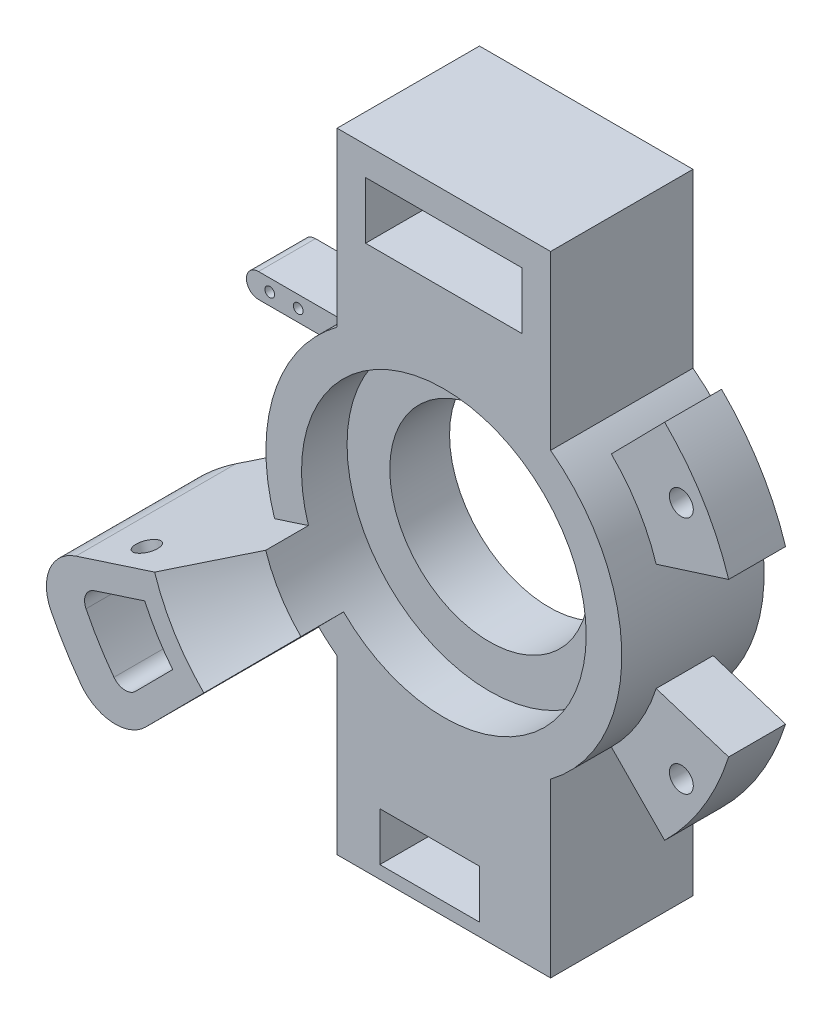
SolidWorks part; units mm, degrees
ref_plane "Front Plane" through (0, 0, 0) normal (0, 0, 1) x (1, 0, 0)
ref_plane "Top Plane" through (0, 0, 0) normal (0, 1, 0) x (1, 0, 0)
ref_plane "Right Plane" through (0, 0, 0) normal (1, 0, 0) x (0, 0, -1)
sketch "Sketch1" plane through (0, 0, 0) normal (0, 1, 0) x (1, 0, 0)
  line L1 (-37.5, -25) -> (37.5, -25)
  line L2 (-37.5, -25) -> (-37.5, 25)
  line L3 (-37.5, 25) -> (37.5, 25)
  line L4 (37.5, -25) -> (37.5, 25)
  line L5 (-37.5, -25) -> (37.5, 25) construction
  line L6 (-37.5, 25) -> (37.5, -25) construction
  point P0 (0, 0)
  dimension "D1" = 50
  dimension "D2" = 75
extrude "BE - main upright body" add sketch "Sketch1" along normal blind 221 contours L3 L4 L1 L2
sketch "Sketch2" plane through (0, 0, 25) normal (0, 0, 1) x (1, 0, 0)
  line L0 (-37.5, 221) -> (37.5, 0) construction
  line L1 (-37.5, 0) -> (37.5, 221) construction
  circle A0 centre (0, 110.5) radius 50
  point P10 (0, 110.5)
  dimension "D1" = 100
sketch "Sketch3" plane through (0, 0, -25) normal (0, 0, -1) x (-1, 0, 0)
  line L0 (-37.5, 0) -> (37.5, 221) construction
  line L1 (-37.5, 221) -> (37.5, 0) construction
  circle A0 centre (0, 110.5) radius 55
  point P10 (0, 110.5)
  dimension "D1" = 110
sketch "Sketch19" plane through (0, 0, 25) normal (0, 0, 1) x (1, 0, 0)
  line L0 (-37.5, 221) -> (37.5, 0) construction
  line L1 (-37.5, 0) -> (37.5, 221) construction
  circle A0 centre (0, 110.5) radius 62.5
  point P11 (0, 110.5)
  dimension "D1" = 125
extrude "Boss-Extrude1" add sketch "Sketch19" against normal up to surface (50 mm away) up to face at (0, 110.5, -25)
sketch "Sketch4" plane through (0, 0, 25) normal (0, 0, 1) x (1, 0, 0)
  line L0 (-37.5, 221) -> (37.5, 0) construction
  line L1 (37.5, 221) -> (-37.5, 0) construction
  line L2 (-37.5, 0) -> (37.5, 0) construction
  circle A0 centre (0, 110.5) radius 35
  dimension "D1" = 70
extrude "CE - Through hole" cut sketch "Sketch4" against normal through all
extrude "CE - Inner bearing" cut sketch "Sketch2" against normal blind 16 contours A0
extrude "CE - Outer bearing" cut sketch "Sketch3" against normal blind 13 contours A0
sketch "Sketch23" plane through (0, 0, 0) normal (0, 0, 1) x (1, 0, 0)
  line L0 (35.0571, 146.1511) -> (62.549, 174.1087)
  line L1 (47.6561, 125.6292) -> (85.0282, 137.4935)
  line L2 (0, 110.5) -> (35.0571, 146.1511) construction
  line L3 (0, 110.5) -> (47.6561, 125.6292) construction
  line L6 (35.0571, 74.8489) -> (62.549, 46.8913)
  line L7 (47.6561, 95.3708) -> (85.0282, 83.5065)
  line L8 (0, 110.5) -> (230.7958, 110.5) construction
  line L9 (85.0282, 137.4935) -> (85.0282, 83.5065) construction
  line L10 (0, 110.5) -> (47.6561, 95.3708) construction
  line L11 (0, 110.5) -> (35.0571, 74.8489) construction
  line L12 (43.8214, 155.0638) -> (85.0282, 137.4935) construction
  line L13 (59.5702, 129.4115) -> (62.549, 174.1087) construction
  line L14 (59.5702, 91.5885) -> (62.549, 46.8913) construction
  line L15 (43.8214, 65.9362) -> (85.0282, 83.5065) construction
  line L17 (76.0258, 157.1746) -> (60.7974, 147.8254) construction
  line L18 (60.7974, 73.1746) -> (76.0258, 63.8254) construction
  arc A0 (35.0571, 146.1511) -> (47.6561, 125.6292) centre (0, 110.5) cw
  arc A1 (85.0282, 137.4935) -> (62.549, 174.1087) centre (0, 110.5) ccw
  arc A2 (37.5, 60.5) -> (37.5, 160.5) centre (0, 110.5) ccw construction
  arc A3 (43.8214, 65.9362) -> (59.5702, 91.5885) centre (0, 110.5) ccw construction
  arc A6 (35.0571, 74.8489) -> (47.6561, 95.3708) centre (0, 110.5) ccw
  arc A7 (85.0282, 83.5065) -> (62.549, 46.8913) centre (0, 110.5) cw
  circle A8 centre (0, 110.5) radius 50 construction
  arc A9 (59.5702, 129.4115) -> (43.8214, 155.0638) centre (0, 110.5) ccw construction
  point P1 (85.0282, 110.5)
  point P4 (60.7974, 147.8254)
  point P9 (60.7974, 73.1746)
  point P20 (68.4116, 152.5)
  point P21 (68.4116, 68.5)
  point P24 (93.6055, 142.1921)
  point P26 (92.1151, 140.9355)
  point P28 (85.0282, 137.4935)
  dimension "D1" = 84
extrude "BE - caliper mount v2" add sketch "Sketch23" along normal mid plane 20
sketch "Sketch24" plane through (0, 0, 0) normal (0, 0, 1) x (1, 0, 0)
  line L0 (-35.2168, 75.0066) -> (-81.1221, 28.7407)
  line L1 (-47.5666, 95.0916) -> (-109.5701, 75.0066)
  line L2 (0, 110.5) -> (-35.2168, 75.0066) construction
  line L3 (0, 110.5) -> (-47.5666, 95.0916) construction
  line L8 (0, 110.5) -> (230.7958, 110.5) construction
  arc A0 (-35.2168, 75.0066) -> (-47.5666, 95.0916) centre (0, 110.5) cw
  arc A1 (-109.5701, 75.0066) -> (-81.1221, 28.7407) centre (0, 110.5) ccw
  circle A2 centre (0, 110.5) radius 50 construction
  point P1 (-109.5701, 75.0066)
extrude "BE - tie rod mount v2" add sketch "Sketch24" along normal blind 60 and the other way blind 10
sketch "Sketch32" plane through (0, 0, 0) normal (0, 0, 1) x (1, 0, 0)
  line L0 (-40.309, 148.6044) -> (-80.0947, 148.6044)
  line L1 (-80.0947, 140.0836) -> (-40.309, 140.0836)
  line L2 (-40.309, 148.6044) -> (-40.309, 140.0836)
  arc A0 (-80.0947, 148.6044) -> (-80.0947, 140.0836) centre (-80.0947, 144.344) ccw
  circle A1 centre (0, 110.5) radius 50 construction
  circle A2 centre (-76.1523, 144.344) radius 1.7
  circle A3 centre (-66.1523, 144.344) radius 1.7
  point P10 (-82.3567, 150.8583)
  point P11 (-74.3506, 151.9485)
  point P13 (-72.6596, 146.8613)
  point P14 (-74.4213, 148.1665)
  point P15 (-80.0947, 148.808)
  point P16 (-76.1523, 144.344)
  dimension "D1" = 10
  dimension "D2" = 3.4
extrude "BE - temp sensor mount v3" add sketch "Sketch32" along normal mid plane 20
sketch "Sketch12" plane through (0, 0, 25) normal (0, 0, 1) x (1, 0, 0)
  line L0 (-12.5, 201) -> (12.5, 201) construction
  line L2 (-37.5, 221) -> (37.5, 221) construction
  circle A0 centre (-12.5, 201) radius 4
  circle A1 centre (12.5, 201) radius 4
  point P2 (0, 201)
  dimension "D1" = 8
  dimension "D2" = 20
  dimension "D3" = 25
sketch "Sketch26" plane through (0, 0, 0) normal (0, 0, 1) x (1, 0, 0)
  line L0 (59.5702, 129.4115) -> (85.0282, 137.4935) construction
  line L1 (62.549, 174.1087) -> (43.8214, 155.0638) construction
  line L2 (59.5702, 129.4115) -> (85.0282, 137.4935) construction
  line L3 (62.549, 174.1087) -> (43.8214, 155.0638) construction
  line L4 (62.549, 174.1087) -> (59.5702, 129.4115) construction
  line L5 (43.8214, 155.0638) -> (85.0282, 137.4935) construction
  line L6 (0, 110.5) -> (188.9632, 110.5) construction
  line L7 (59.5702, 91.5885) -> (85.0282, 83.5065) construction
  line L8 (62.549, 46.8913) -> (43.8214, 65.9362) construction
  line L9 (43.8214, 65.9362) -> (85.0282, 83.5065) construction
  line L10 (62.549, 46.8913) -> (59.5702, 91.5885) construction
  line L11 (60.7974, 147.8254) -> (76.0258, 157.1746) construction
  line L12 (60.7974, 73.1746) -> (76.0258, 63.8254) construction
  arc A2 (59.5702, 129.4115) -> (43.8214, 155.0638) centre (0, 110.5) ccw construction
  arc A3 (85.0282, 137.4935) -> (62.549, 174.1087) centre (0, 110.5) ccw construction
  arc A4 (59.5702, 129.4115) -> (43.8214, 155.0638) centre (0, 110.5) ccw construction
  arc A5 (85.0282, 137.4935) -> (62.549, 174.1087) centre (0, 110.5) ccw construction
  arc A6 (85.0282, 83.5065) -> (62.549, 46.8913) centre (0, 110.5) cw construction
  arc A7 (59.5702, 91.5885) -> (43.8214, 65.9362) centre (0, 110.5) cw construction
  circle A9 centre (68.4116, 68.5) radius 4.2
  circle A10 centre (68.4116, 152.5) radius 4.2
  point P2 (60.7974, 73.1746)
  point P7 (60.7974, 147.8254)
  point P17 (79.7073, 34.6249)
  dimension "D1" = 8.4
extrude "CE - caliper holes" cut sketch "Sketch26" against normal up to next and the other way up to next contours A10 | A9
extrude "CE - top clevis holes" cut sketch "Sketch12" against normal through all
sketch "Sketch13" plane through (0, 0, 25) normal (0, 0, 1) x (1, 0, 0)
  line L0 (-37.5, 221) -> (37.5, 221) construction
  line L1 (-27.5, 191) -> (27.5, 191)
  line L2 (-27.5, 191) -> (-27.5, 211)
  line L3 (-27.5, 211) -> (27.5, 211)
  line L4 (27.5, 191) -> (27.5, 211)
  line L5 (-27.5, 191) -> (27.5, 211) construction
  line L6 (-27.5, 211) -> (27.5, 191) construction
  point P0 (0, 201)
  dimension "D1" = 20
  dimension "D2" = 55
  dimension "D3" = 20
extrude "CE - top clevis space" cut sketch "Sketch13" against normal blind 35 contours L3 L4 L1 L2
ref_plane "Top clevis plane" through (0, 0, 5) normal (0, 0, 1) x (1, 0, 0)
ref_point "Position of Top Clevis"
sketch "Sketch14" plane through (0, 0, 25) normal (0, 0, 1) x (1, 0, 0)
  line L1 (-22.48, 4.5) -> (2.52, 4.5)
  line L2 (-22.48, 4.5) -> (-22.48, 16.5)
  line L3 (-22.48, 16.5) -> (2.52, 16.5)
  line L4 (2.52, 4.5) -> (2.52, 16.5)
  line L5 (-22.48, 4.5) -> (2.52, 16.5) construction
  line L6 (-22.48, 16.5) -> (2.52, 4.5) construction
  point P0 (-9.98, 10.5)
  dimension "D1" = 9.98
  dimension "D2" = 190.5
  dimension "D3" = 12
  dimension "D4" = 25
extrude "CE - bottom clevis space" cut sketch "Sketch14" against normal through all
ref_plane "Bottom Clevis Plane" through (0, 0, -1.65) normal (0, 0, 1) x (1, 0, 0)
ref_point "Position of Bottom Clevis"
ref_plane "P - xy plane containing bottom clevis" through (0, 10.5, 0) normal (0, -1, 0) x (-1, 0, 0)
ref_plane "P - xy plane containing tie rod" through (0, 63.84, 0) normal (0, -1, 0) x (-1, 0, 0)
ref_plane "P - front of part" through (2.52, 4.5, 25) normal (0, 0, 1) x (1, 0, 0)
sketch "Sketch15" plane through (0, 0, 25) normal (0, 0, 1) x (1, 0, 0)
  line L0 (2.52, 4.5) -> (2.52, 16.5) construction
  line L1 (-22.48, 16.5) -> (2.52, 16.5)
  line L2 (-22.48, 16.5) -> (-22.48, 21.5)
  line L3 (-22.48, 21.5) -> (2.52, 21.5)
  line L4 (2.52, 16.5) -> (2.52, 21.5)
  dimension "D1" = 5
extrude "CE - expand bottom clevis" cut sketch "Sketch15" against normal through all
sketch "Sketch16" plane through (2.52, 4.5, 25) normal (0, 0, 1) x (1, 0, 0)
  line L0 (0, 17) -> (-25, 17) construction
  line L1 (0, 0) -> (10.0076, 0)
  line L2 (0, 0) -> (0, 17)
  line L3 (0, 17) -> (10.0076, 17)
  line L4 (10.0076, 0) -> (10.0076, 17)
  dimension "D1" = 10.0076
extrude "CE - widen bottom clevis" cut sketch "Sketch16" against normal through all and the other way through all
sketch "Sketch17" plane through (0, 63.84, 0) normal (0, -1, 0) x (-1, 0, 0)
  point P0 (73.48, -49.15)
  point P1 (9.98, 1.65)
  point P3 (9.98, 1.65)
  dimension "D1" = 63.5
  dimension "D2" = 50.8
ref_point "Position of Tie Rod"
sketch "Sketch18" [suppressed] plane through (0, 0, 55) normal (0, 0, 1) x (1, 0, 0)
  line L1 (-80.502, 57.0586) -> (-66.458, 57.0586)
  line L2 (-80.502, 57.0586) -> (-80.502, 70.6214)
  line L3 (-80.502, 70.6214) -> (-66.458, 70.6214)
  line L4 (-66.458, 57.0586) -> (-66.458, 70.6214)
  line L5 (-80.502, 57.0586) -> (-66.458, 70.6214) construction
  line L6 (-80.502, 70.6214) -> (-66.458, 57.0586) construction
  point P0 (-73.48, 63.84)
  point P2 (-73.48, 63.84)
chamfer "Chamfer1" distance 20 angle 45 1 edges at (-42.5925, 84.3107, 60)
chamfer "Chamfer2" distance 30 angle 45 1 edges at (-98.1122, 50.1728, -10)
sketch "Sketch28" plane through (-32.3953, 100.0061, 0) normal (-0.3082, 0.9513, 0) x (0.9513, 0.3082, 0)
  circle A0 centre (-50.2304, -49.15) radius 4
  point P0 (-50.2304, -49.15)
  dimension "D1" = 8
extrude "Cut-Extrude1" cut sketch "Sketch28" against normal up to next contours A0
sketch "Sketch29" plane through (0, 0, 60) normal (0, 0, 1) x (1, 0, 0)
  line L0 (-70.0705, 78.4191) -> (-93.0797, 70.9656)
  line L1 (-60.2509, 62.449) -> (-77.2861, 45.2799)
  line L2 (-66.5932, 88.9282) -> (-109.5701, 75.0066) construction
  line L3 (-81.1221, 28.7407) -> (-49.3035, 60.8093) construction
  line L4 (-93.0797, 70.9656) -> (-95.8305, 79.4573) construction
  line L6 (-77.2861, 45.2799) -> (-70.9498, 38.993) construction
  line L8 (-70.0705, 78.4191) -> (-77.2861, 45.2799) construction
  line L9 (-93.0797, 70.9656) -> (-60.2509, 62.449) construction
  arc A1 (-93.0797, 70.9656) -> (-77.2861, 45.2799) centre (0, 110.5) ccw
  arc A2 (-109.5701, 75.0066) -> (-81.1221, 28.7407) centre (0, 110.5) ccw construction
  arc A3 (-70.0705, 78.4191) -> (-60.2509, 62.449) centre (0, 110.5) ccw
  arc A4 (-66.5932, 88.9282) -> (-49.3035, 60.8093) centre (0, 110.5) ccw construction
  point P5 (-73.48, 63.84)
  point P12 (-72.8369, 65.7141)
  point P13 (-73.48, 63.84)
  point P20 (-73.48, 63.84)
  point P21 (-60.2509, 62.449)
extrude "Cut-Extrude2" cut sketch "Sketch29" against normal up to next
fillet "Fillet1" [suppressed] radius 15
fillet "Fillet2" radius 15 2 edges at (-81.1221, 28.7407, 40) (-109.5701, 75.0066, 40)
fillet "Fillet3" radius 5 2 edges at (-77.2861, 45.2799, 32.9761) (-93.0797, 70.9656, 32.9761)
equation "\"clevis_pin_y\"=20"
equation "\"D2@Sketch12\"=\"clevis_pin_y\""
equation "\"clevis_pin_dist\"=25"
equation "\"D3@Sketch12\"=\"clevis_pin_dist\""
equation "\"D2@Sketch13\"=\"clevis_pin_dist\" + 30"
equation "\"D1@Sketch13\"=\"clevis_pin_y\""
equation "\"x_dist_a_arms\"=9.98"
equation "\"D1@Sketch14\"=\"x_dist_a_arms\""
equation "\"y_dist_a_arms\"=190.5"
equation "\"D2@Sketch14\"=\"y_dist_a_arms\""
equation "\"y_dist_bottom_clevis_to_tie_rod\"= 53.34"
equation "\"x_dist_bottom_clevis_to_tie_rod\"= 63.50"
equation "\"z_dist_bottom_clevis_to_tie_rod\"= 50.80"
